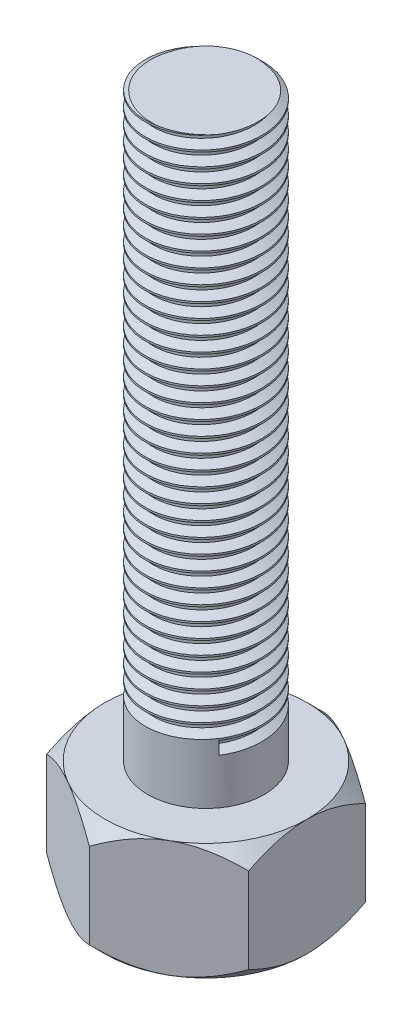
SolidWorks part; units mm, degrees
ref_plane "Front Plane" through (0, 0, 0) normal (0, 0, 1) x (1, 0, 0)
ref_plane "Top Plane" through (0, 0, 0) normal (0, 1, 0) x (1, 0, 0)
ref_plane "Right Plane" through (0, 0, 0) normal (1, 0, 0) x (0, 0, -1)
sketch "Sketch1" plane through (0, 0, 0) normal (0, 1, 0) x (1, 0, 0)
  line L1 (8.6603, -5) -> (8.6603, 5)
  line L2 (8.6603, 5) -> (0, 10)
  line L3 (0, 10) -> (-8.6603, 5)
  line L4 (-8.6603, 5) -> (-8.6603, -5)
  line L5 (-8.6603, -5) -> (0, -10)
  line L6 (0, -10) -> (8.6603, -5)
  circle A0 centre (0, 0) radius 8.6603 construction
  dimension "D2" = 10
extrude "Boss-Extrude1" add sketch "Sketch1" along normal mid plane 10
sketch "Sketch3" plane through (0, -5, 0) normal (0, -1, 0) x (1, 0, 0)
  line L0 (-8.6603, 5) -> (0, 10) construction
  circle A1 centre (0, 0) radius 8.6603
extrude "Cut-Extrude2" cut sketch "Sketch3" against normal blind 10 draft 45 flip side to cut
mirror "Mirror1" about plane through (0, 0, 0) normal (0, 1, 0) of "Cut-Extrude2"
sketch "Sketch4" plane through (0, 5, 0) normal (0, 1, 0) x (1, 0, 0)
  circle A0 centre (0, 0) radius 5
  dimension "D1" = 10
extrude "Boss-Extrude2" add sketch "Sketch4" along normal blind 50
thread "Thread1" pitch 1.25 method cut profile "Thread Profile1" start angle 0, offset 2, length 47, pitch 1.25, diameter 10
ref_plane "Plane1" through (-5, 57, 0) normal (0, 0, 1) x (-1, 0, 0)
sketch "Thread Profile1" plane through (-5, 57, 0) normal (0, 0, 1) x (-1, 0, 0)
  line L0 (0, 0) -> (0, 1.25) construction
  line L11 (0, 0) -> (0, 1.0937)
  line L12 (0, 1.0937) -> (-0.6766, 0.7031)
  line L13 (-0.6766, 0.7031) -> (-0.6766, 0.3906)
  line L15 (-0.6766, 0.3906) -> (0, 0)
  line L17 (-0.6766, 0.5469) -> (0, 0.5469) construction
  point P2 (0, 0)
  dimension "Pitch" = 1.25
  dimension "Profile_Angle" = 60
  dimension "Profile_Land" = 0.3125
  dimension "Profile_Height" = 0.6766
